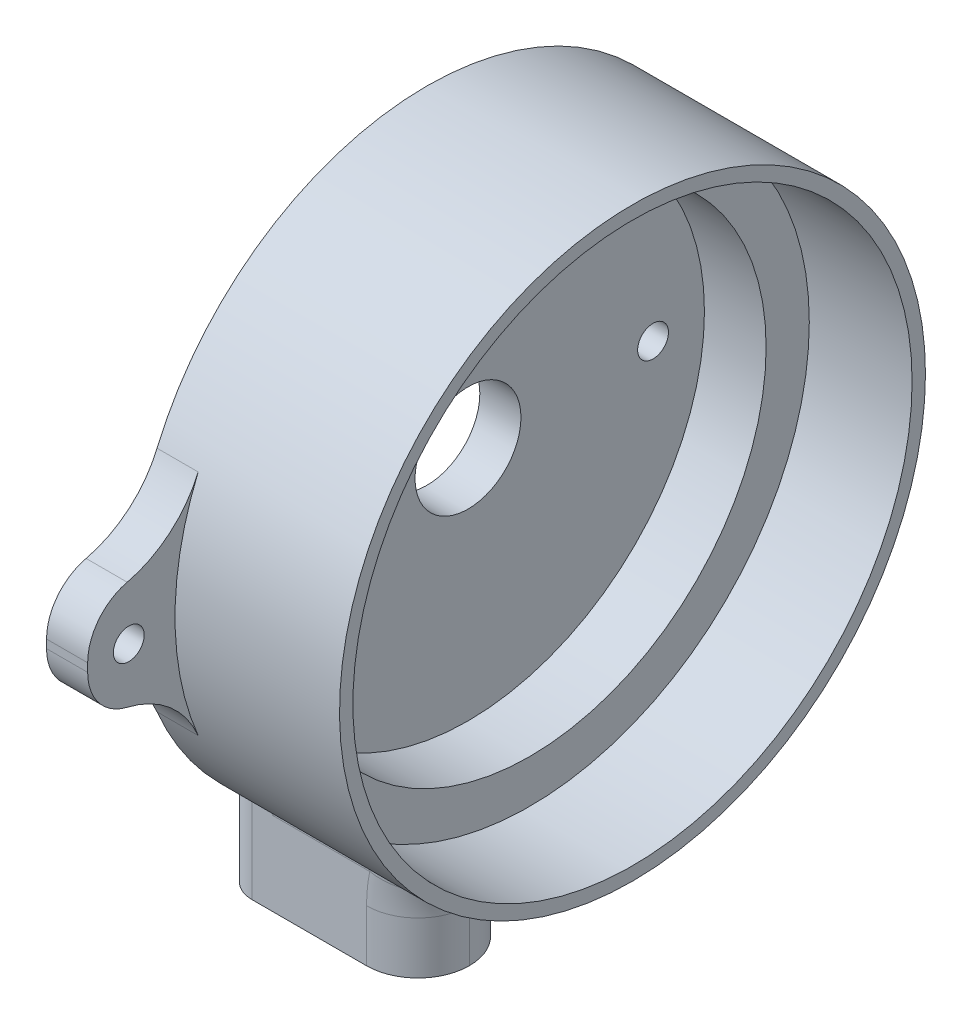
SolidWorks part; units mm, degrees
ref_plane "前视基准面" through (0, 0, 0) normal (0, 0, 1) x (1, 0, 0)
ref_plane "上视基准面" through (0, 0, 0) normal (0, 1, 0) x (1, 0, 0)
ref_plane "右视基准面" through (0, 0, 0) normal (1, 0, 0) x (0, 0, -1)
other "Configuration Table"
sketch "草图1" plane through (0, 0, 0) normal (1, 0, 0) x (0, 0, -1)
  circle A0 centre (0, 0) radius 28.5
  dimension "D1" = 57
extrude "凸台-拉伸1" add sketch "草图1" along normal blind 20
sketch "草图5" plane through (0, 0, 0) normal (-1, 0, 0) x (0, 0, 1)
  line L0 (0, 0) -> (0, 10.6758) construction
  line L1 (0, 0) -> (14.1218, 0) construction
  line L2 (0, 5.0001) -> (37, 5.0001)
  line L3 (-37, 5.0001) -> (0, 5.0001)
  line L4 (-37, 5.0001) -> (-37, -4.9999)
  line L5 (-37, -4.9999) -> (0, -4.9999)
  line L7 (37, 5.0001) -> (37, -4.9999)
  line L8 (37, -4.9999) -> (0, -4.9999)
  dimension "D1" = 37
  dimension "D2" = 10
  dimension "D3" = 5.0001
  dimension "D4" = 37
extrude "凸台-拉伸2" add sketch "草图5" against normal blind 4
sketch "草图2" plane through (20, 0, 0) normal (1, 0, 0) x (0, 0, -1)
  circle A0 centre (0, 0) radius 27.2
  dimension "D1" = 54.4
extrude "切除-拉伸1" cut sketch "草图2" against normal blind 10
sketch "草图3" plane through (10, 0, 0) normal (1, 0, 0) x (0, 0, -1)
  circle A0 centre (0, 0) radius 5.15
  dimension "D1" = 10.3
extrude "切除-拉伸2" cut sketch "草图3" against normal up to next
sketch "草图4" plane through (10, 0, 0) normal (1, 0, 0) x (0, 0, -1)
  circle A0 centre (0, 0) radius 23
  dimension "D1" = 46
extrude "切除-拉伸3" cut sketch "草图4" against normal blind 6
sketch "草图6" plane through (4, 0, 0) normal (1, 0, 0) x (0, 0, -1)
  line L0 (-37, 0.0001) -> (37, 0.0001) construction
  line L1 (-37, -4.9999) -> (-37, 5.0001) construction
  line L2 (37, 5.0001) -> (37, -4.9999) construction
  circle A0 centre (-33, 0.0001) radius 1.5
  circle A1 centre (33, 0.0001) radius 1.5
  dimension "D1" = 3
  dimension "D2" = 3
  dimension "D3" = 4
  dimension "D4" = 4
extrude "切除-拉伸4" cut sketch "草图6" against normal up to next
fillet "圆角1" radius 10 4 edges at (2, 5.0001, -28.058) (2, -4.9999, -28.058) (2, 5.0001, 28.058) (2, -4.9999, 28.058)
fillet "圆角2" radius 5 4 edges at (2, 5.0001, 37) (2, -4.9999, 37) (2, -4.9999, -37) (2, 5.0001, -37)
sketch "草图7" plane through (4, 0, 0) normal (1, 0, 0) x (0, 0, -1)
  line L0 (0, 0) -> (17.2688, 0) construction
  line L1 (0, 0) -> (-19.7613, 0) construction
  circle A1 centre (-18, 0) radius 1.5
  circle A2 centre (18, 0) radius 1.5
  dimension "D1" = 3
  dimension "D2" = 3
  dimension "D3" = 18
  dimension "D4" = 18
extrude "切除-拉伸5" cut sketch "草图7" against normal up to next
sketch "草图8" plane through (0, 0, 0) normal (-1, 0, 0) x (0, 0, 1)
  line L0 (0, 28.5) -> (0, -28.5) construction
  line L6 (-5, -23.058) -> (5, -23.058)
  line L7 (-5, -23.058) -> (-5, -28.058)
  line L8 (-5, -28.058) -> (5, -28.058)
  line L9 (5, -23.058) -> (5, -28.058)
  arc A0 (26.2479, 11.104) -> (-26.2479, 11.104) centre (0, 0) ccw construction
  arc A1 (-26.2479, -11.1038) -> (26.2479, -11.1038) centre (0, 0) ccw construction
  dimension "D1" = 10
  dimension "D2" = 5
extrude "凸台-拉伸3" add sketch "草图8" along normal blind 15
fillet "圆角7" radius 10 3 edges at (0, -25.558, 5) (0, -23.058, 0) (0, -25.558, -5)
sketch "草图10" plane through (0, -28.058, 0) normal (0, -1, 0) x (-1, 0, 0)
  line L1 (15, -5) -> (-4.1294, -5)
  line L2 (15, -5) -> (15, 5)
  line L3 (15, 5) -> (-4.1294, 5)
  line L4 (-4.1294, -5) -> (-4.1294, 5)
extrude "凸台-拉伸4" add sketch "草图10" along normal blind 15.5 and the other way blind 1
sketch "草图9" plane through (0, -28.058, 0) normal (0, -1, 0) x (-1, 0, 0)
  line L0 (15, 0) -> (1.3687, 0) construction
  line L2 (15, -5) -> (15, 5) construction
  circle A0 centre (9, 0) radius 3
  dimension "D1" = 6
  dimension "D2" = 6
extrude "切除-拉伸6" cut sketch "草图9" along normal up to next and the other way blind 14.5
fillet "圆角9" radius 10 3 edges at (4.1294, -28.5, 0) (-2.9353, -28.058, 5) (-2.9353, -28.058, -5)
fillet "圆角10" radius 3 2 edges at (-15, -33.308, 5) (-15, -33.308, -5)
fillet "圆角11" radius 5 6 edges at (8.1128, -29.7472, -6.7908) (8.1128, -29.7472, 6.7908) (4.1294, -40.866, -5) (4.1294, -40.866, 5)
